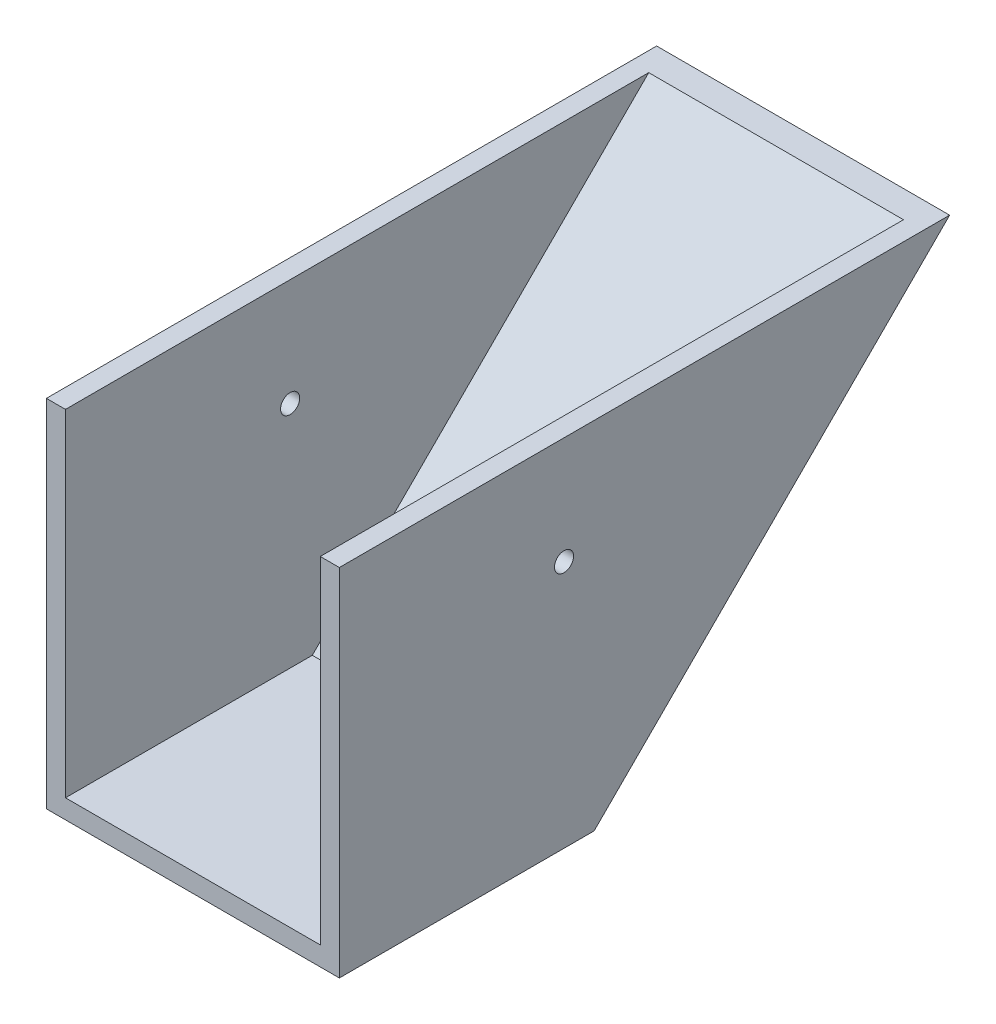
SolidWorks part; units mm, degrees
material "ALUMINUM 6061-T6"
ref_plane "Front Plane" through (0, 0, 0) normal (0, 0, 1) x (1, 0, 0)
ref_plane "Top Plane" through (0, 0, 0) normal (0, 1, 0) x (1, 0, 0)
ref_plane "Right Plane" through (0, 0, 0) normal (1, 0, 0) x (0, 0, -1)
sketch "Sketch2" plane through (0, 0, 0) normal (0, 1, 0) x (1, 0, 0)
  line L1 (-146.05, -317.5) -> (146.05, -317.5)
  line L2 (-146.05, -317.5) -> (-146.05, 317.5)
  line L3 (-146.05, 317.5) -> (146.05, 317.5)
  line L4 (146.05, -317.5) -> (146.05, 317.5)
  line L5 (-146.05, -317.5) -> (146.05, 317.5) construction
  line L6 (-146.05, 317.5) -> (146.05, -317.5) construction
  point P0 (0, 0)
extrude "Boss-Extrude1" add sketch "Sketch2" along normal mid plane 381
sketch "Sketch4" plane through (-146.05, 0, 0) normal (-1, 0, 0) x (0, 0, 1)
  line L0 (-317.5, 190.5) -> (63.5, -190.5)
  line L1 (-317.5, -190.5) -> (317.5, -190.5) construction
  line L2 (-317.5, 190.5) -> (-317.5, -190.5) construction
  line L3 (-317.5, 190.5) -> (-317.5, -190.5)
  line L4 (-317.5, -190.5) -> (63.5, -190.5)
  dimension "D1" = 45
extrude "Cut-Extrude2" cut sketch "Sketch4" against normal blind 381
shell "Shell1" thickness 19.05 removed face at (0, 0, 317.5)
sketch "Sketch5" plane through (0, 190.5, 0) normal (0, 1, 0) x (1, 0, 0)
  line L1 (-146.05, 317.5) -> (146.05, 317.5)
  line L2 (-146.05, 317.5) -> (-146.05, -317.5)
  line L3 (-146.05, -317.5) -> (146.05, -317.5)
  line L4 (146.05, 317.5) -> (146.05, -317.5)
extrude "Cut-Extrude3" cut sketch "Sketch5" against normal blind 24.892
sketch "Sketch6" plane through (-146.05, 0, 0) normal (-1, 0, 0) x (0, 0, 1)
  circle A0 centre (93.5173, 56.9612) radius 9.525
extrude "Cut-Extrude4" cut sketch "Sketch6" against normal blind 514.096
sketch "Sketch10" plane through (0, 165.608, 0) normal (0, 1, 0) x (1, 0, 0)
  line L1 (-146.05, 292.608) -> (146.05, 292.608)
  line L2 (-146.05, 292.608) -> (-146.05, -317.5)
  line L3 (-146.05, -317.5) -> (146.05, -317.5)
  line L4 (146.05, 292.608) -> (146.05, -317.5)
extrude "Cut-Extrude7" cut sketch "Sketch10" against normal blind 1.6933
